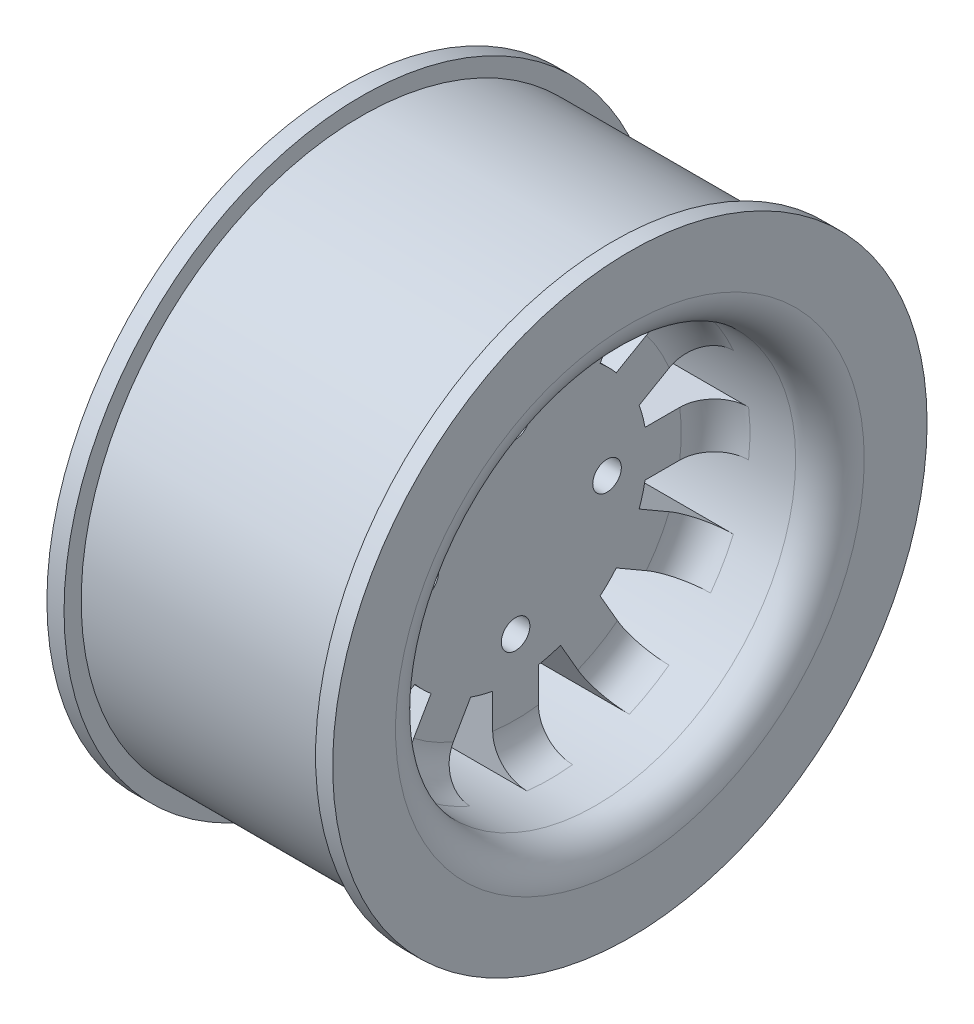
SolidWorks part; units mm, degrees
ref_plane "前视基准面" through (0, 0, 0) normal (0, 0, 1) x (1, 0, 0)
ref_plane "上视基准面" through (0, 0, 0) normal (0, 1, 0) x (1, 0, 0)
ref_plane "右视基准面" through (0, 0, 0) normal (1, 0, 0) x (0, 0, -1)
sketch "草图1" plane through (0, 0, 0) normal (1, 0, 0) x (0, 0, -1)
  circle A0 centre (0, 0) radius 24.5
  dimension "D1" = 49
extrude "凸台-拉伸1" add sketch "草图1" along normal blind 22
sketch "草图2" plane through (22, 0, 0) normal (1, 0, 0) x (0, 0, -1)
  circle A0 centre (0, 0) radius 26
  dimension "D1" = 52
extrude "凸台-拉伸2" add sketch "草图2" along normal blind 1.5
sketch "草图3" plane through (0, 0, 0) normal (-1, 0, 0) x (0, 0, 1)
  circle A0 centre (0, 0) radius 26
extrude "凸台-拉伸3" add sketch "草图3" along normal blind 1.5
sketch "草图4" plane through (-1.5, 0, 0) normal (-1, 0, 0) x (0, 0, 1)
  circle A0 centre (0, 0) radius 17.5
  dimension "D1" = 35
extrude "切除-拉伸1" cut sketch "草图4" against normal blind 10
sketch "草图5" plane through (8.5, 0, 0) normal (-1, 0, 0) x (0, 0, 1)
  line L0 (-19.9141, 0) -> (20.9752, 0) construction
  line L1 (0, -21.0106) -> (0, 22.1425) construction
  circle A0 centre (0, 0) radius 8 construction
  circle A1 centre (0, 8) radius 1.25
  circle A2 centre (8, 0) radius 1.25
  circle A3 centre (0, -8) radius 1.25
  circle A4 centre (-8, 0) radius 1.25
  point P19 (0, 0)
  dimension "D1" = 16
  dimension "D2" = 2.5
  dimension "D3" = 4
extrude "切除-拉伸2" cut sketch "草图5" against normal through all
sketch "草图6" plane through (8.5, 0, 0) normal (-1, 0, 0) x (0, 0, 1)
  circle A0 centre (0, 0) radius 4.3
  circle A1 centre (0, 0) radius 2.5
  dimension "D1" = 8.6
  dimension "D2" = 5
extrude "凸台-拉伸4" add sketch "草图6" along normal through all
sketch "草图7" plane through (23.5, 0, 0) normal (1, 0, 0) x (0, 0, -1)
  circle A0 centre (0, 0) radius 17.5
  dimension "D1" = 35
extrude "切除-拉伸3" cut sketch "草图7" against normal blind 10
sketch "草图8" plane through (13.5, 0, 0) normal (1, 0, 0) x (0, 0, -1)
  line L0 (0, -11.5) -> (0, 20.7984) construction
  line L1 (2, 11.3248) -> (2, 17.3853)
  line L2 (-2, 11.3248) -> (-2, 17.3853)
  line L3 (7.3944, 8.8075) -> (10.4247, 14.0561)
  line L4 (3.9303, 10.8075) -> (6.9606, 16.0561)
  line L5 (10.8075, 3.9303) -> (16.0561, 6.9606)
  line L6 (8.8075, 7.3944) -> (14.0561, 10.4247)
  line L7 (11.3248, -2) -> (17.3853, -2)
  line L8 (11.3248, 2) -> (17.3853, 2)
  line L9 (8.8075, -7.3944) -> (14.0561, -10.4247)
  line L10 (10.8075, -3.9303) -> (16.0561, -6.9606)
  line L11 (3.9303, -10.8075) -> (6.9606, -16.0561)
  line L12 (7.3944, -8.8075) -> (10.4247, -14.0561)
  line L13 (-2, -11.3248) -> (-2, -17.3853)
  line L14 (2, -11.3248) -> (2, -17.3853)
  line L15 (-7.3944, -8.8075) -> (-10.4247, -14.0561)
  line L16 (-3.9303, -10.8075) -> (-6.9606, -16.0561)
  line L17 (-10.8075, -3.9303) -> (-16.0561, -6.9606)
  line L18 (-8.8075, -7.3944) -> (-14.0561, -10.4247)
  line L19 (-11.3248, 2) -> (-17.3853, 2)
  line L20 (-11.3248, -2) -> (-17.3853, -2)
  line L21 (-8.8075, 7.3944) -> (-14.0561, 10.4247)
  line L22 (-10.8075, 3.9303) -> (-16.0561, 6.9606)
  line L23 (-3.9303, 10.8075) -> (-6.9606, 16.0561)
  line L24 (-7.3944, 8.8075) -> (-10.4247, 14.0561)
  arc A0 (-2, 11.3248) -> (-3.9303, 10.8075) centre (0, 0) ccw
  circle A1 centre (0, 0) radius 17.5 construction
  arc A2 (-2, 17.3853) -> (-6.9606, 16.0561) centre (0, 0) ccw
  arc A3 (3.9303, 10.8075) -> (2, 11.3248) centre (0, 0) ccw
  arc A4 (6.9606, 16.0561) -> (2, 17.3853) centre (0, 0) ccw
  arc A5 (8.8075, 7.3944) -> (7.3944, 8.8075) centre (0, 0) ccw
  arc A6 (14.0561, 10.4247) -> (10.4247, 14.0561) centre (0, 0) ccw
  arc A7 (11.3248, 2) -> (10.8075, 3.9303) centre (0, 0) ccw
  arc A8 (17.3853, 2) -> (16.0561, 6.9606) centre (0, 0) ccw
  arc A9 (10.8075, -3.9303) -> (11.3248, -2) centre (0, 0) ccw
  arc A10 (16.0561, -6.9606) -> (17.3853, -2) centre (0, 0) ccw
  arc A11 (7.3944, -8.8075) -> (8.8075, -7.3944) centre (0, 0) ccw
  arc A12 (10.4247, -14.0561) -> (14.0561, -10.4247) centre (0, 0) ccw
  arc A13 (2, -11.3248) -> (3.9303, -10.8075) centre (0, 0) ccw
  arc A14 (2, -17.3853) -> (6.9606, -16.0561) centre (0, 0) ccw
  arc A15 (-3.9303, -10.8075) -> (-2, -11.3248) centre (0, 0) ccw
  arc A16 (-6.9606, -16.0561) -> (-2, -17.3853) centre (0, 0) ccw
  arc A17 (-14.0561, -10.4247) -> (-10.4247, -14.0561) centre (0, 0) ccw
  arc A18 (-8.8075, -7.3944) -> (-7.3944, -8.8075) centre (0, 0) ccw
  arc A19 (-11.3248, -2) -> (-10.8075, -3.9303) centre (0, 0) ccw
  arc A20 (-17.3853, -2) -> (-16.0561, -6.9606) centre (0, 0) ccw
  arc A21 (-10.8075, 3.9303) -> (-11.3248, 2) centre (0, 0) ccw
  arc A22 (-16.0561, 6.9606) -> (-17.3853, 2) centre (0, 0) ccw
  arc A23 (-7.3944, 8.8075) -> (-8.8075, 7.3944) centre (0, 0) ccw
  arc A24 (-10.4247, 14.0561) -> (-14.0561, 10.4247) centre (0, 0) ccw
  point P57 (0, 0)
  dimension "D1" = 23
  dimension "D2" = 2
  dimension "D3" = 2
  dimension "D4" = 12
extrude "切除-拉伸4" cut sketch "草图8" against normal through all
fillet "圆角1" radius 3 12 edges at (13.5, 15.1554, 8.75) (13.5, 17.5, 0) (13.5, 15.1554, -8.75) (13.5, 8.75, -15.1554) (13.5, 0, -17.5) (13.5, -8.75, -15.1554) (13.5, -15.1554, -8.75) (13.5, -17.5, 0) (13.5, -15.1554, 8.75) (13.5, -8.75, 15.1554) (13.5, 0, 17.5) (13.5, 8.75, 15.1554)
fillet "圆角2" radius 3 2 edges at (-1.5, 0, 17.5) (23.5, 0, -17.5)
